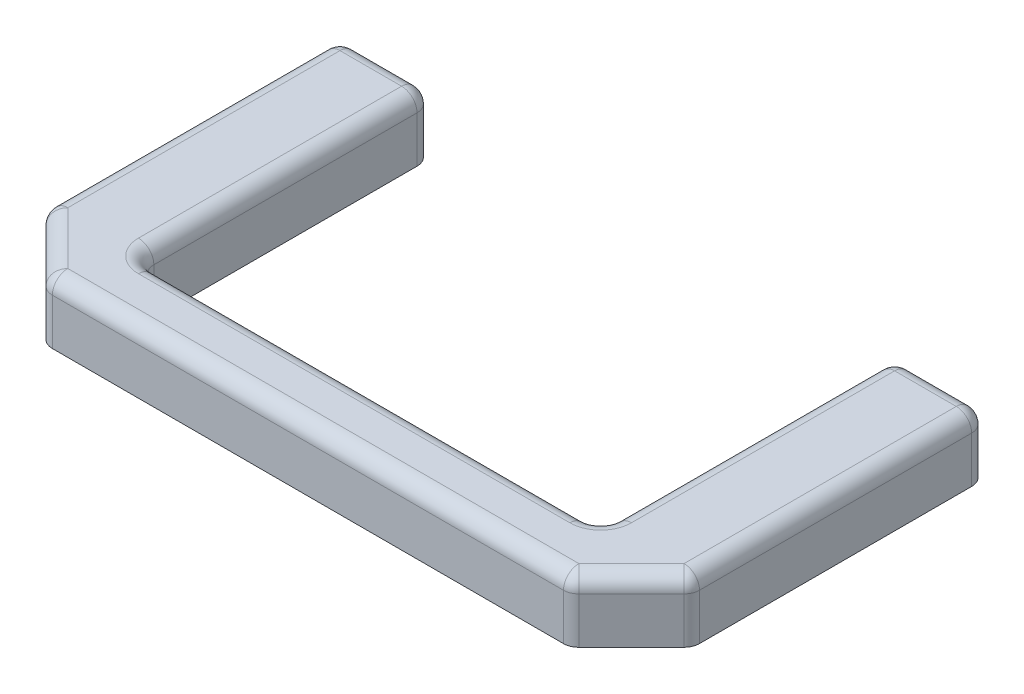
SolidWorks part; units mm, degrees
ref_plane "Front Plane" through (0, 0, 0) normal (0, 0, 1) x (1, 0, 0)
ref_plane "Top Plane" through (0, 0, 0) normal (0, 1, 0) x (1, 0, 0)
ref_plane "Right Plane" through (0, 0, 0) normal (1, 0, 0) x (0, 0, -1)
sketch "Sketch1" plane through (0, 0, 0) normal (0, 1, 0) x (1, 0, 0)
  line L0 (-33.3375, 0) -> (33.3375, 0)
  line L1 (-33.3375, 0) -> (-33.3375, 36.6395)
  line L2 (-33.3375, 36.6395) -> (-23.8125, 36.6395)
  line L3 (-23.8125, 36.6395) -> (-23.8125, 6.35)
  line L4 (-23.8125, 6.35) -> (23.8125, 6.35)
  line L5 (23.8125, 6.35) -> (23.8125, 36.6395)
  line L6 (23.8125, 36.6395) -> (33.3375, 36.6395)
  line L7 (33.3375, 36.6395) -> (33.3375, 0)
  point P3 (0, 0)
  dimension "D1" = 47.625
  dimension "D2" = 9.525
  dimension "D3" = 6.35
  dimension "D4" = 30.2895
extrude "Boss-Extrude1" add sketch "Sketch1" along normal blind 6.35
sketch "Sketch2" plane through (0, 0, -36.6395) normal (0, 0, -1) x (-1, 0, 0)
  line L0 (-33.3375, 6.35) -> (-23.8125, 6.35) construction
  line L1 (-33.3375, 6.35) -> (-33.3375, 0) construction
  circle A0 centre (-28.575, 3.175) radius 1.905
  point P2 (0, 0)
  point P5 (-28.575, 6.35)
  point P8 (-33.3375, 3.175)
  dimension "D1" = 3.81
extrude "Cut-Extrude1" cut sketch "Sketch2" against normal blind 6.35
mirror "Mirror1" about plane through (0, 0, 0) normal (1, 0, 0) of "Cut-Extrude1"
chamfer "Chamfer1" distance 6.35 angle 45 2 edges at (-33.3375, 3.175, 0) (33.3375, 3.175, 0)
fillet "Fillet2" radius 1.5875 20 edges at (-28.575, 6.35, -36.6395) (-23.8125, 6.35, -21.4947) (0, 6.35, -6.35) (23.8125, 6.35, -21.4948) (28.575, 6.35, -36.6395) (33.3375, 6.35, -21.4948) (30.1625, 6.35, -3.175) (0, 6.35, 0) (-30.1625, 6.35, -3.175) (-33.3375, 6.35, -21.4948) (26.9875, 3.175, 0) (33.3375, 3.175, -6.35) (-26.9875, 3.175, 0) (-33.3375, 3.175, -6.35) (-33.3375, 3.175, -36.6395) (-23.8125, 3.175, -36.6395) (33.3375, 3.175, -36.6395) (23.8125, 3.175, -36.6395) (23.8125, 3.175, -6.35) (-23.8125, 3.175, -6.35)
